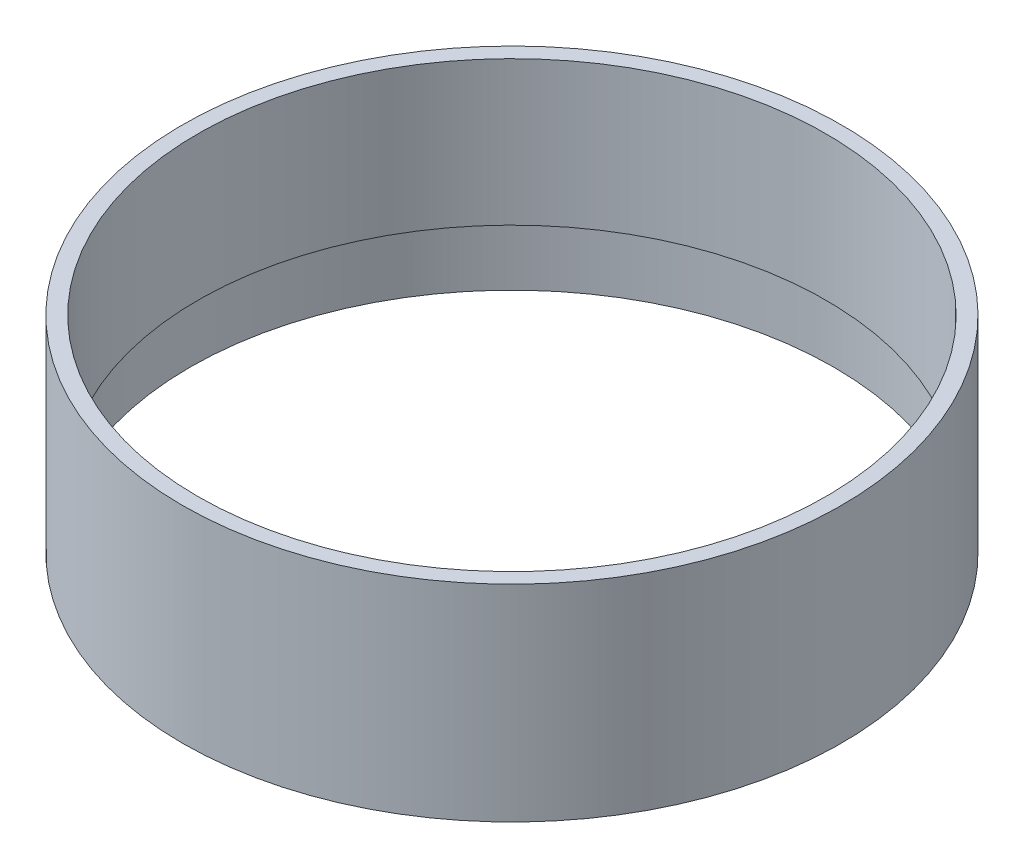
SolidWorks part; units mm, degrees
ref_plane "Front Plane" through (0, 0, 0) normal (0, 0, 1) x (1, 0, 0)
ref_plane "Top Plane" through (0, 0, 0) normal (0, 1, 0) x (1, 0, 0)
ref_plane "Right Plane" through (0, 0, 0) normal (1, 0, 0) x (0, 0, -1)
sketch "Sketch1" plane through (0, 0, 0) normal (0, 1, 0) x (1, 0, 0)
  circle A0 centre (0, 0) radius 15.25
  circle A1 centre (0, 0) radius 16
  circle A2 centre (0, 0) radius 15.625
  dimension "D1" = 30.5
  dimension "D2" = 32
  dimension "D3" = 31.25
extrude "Boss-Extrude1" add sketch "Sketch1" along normal blind 10 contours A1 A2 | A2 A0 region at (-15.9547, 0, 0) region at (-15.5808, 0, 0)
extrude "Cut-Extrude1" cut sketch "Sketch1<6>" along normal blind 3 contours A2
sketch "Sketch1<6>" plane through (0, 0, 0) normal (0, 1, 0) x (1, 0, 0) same geometry as "Sketch1"
